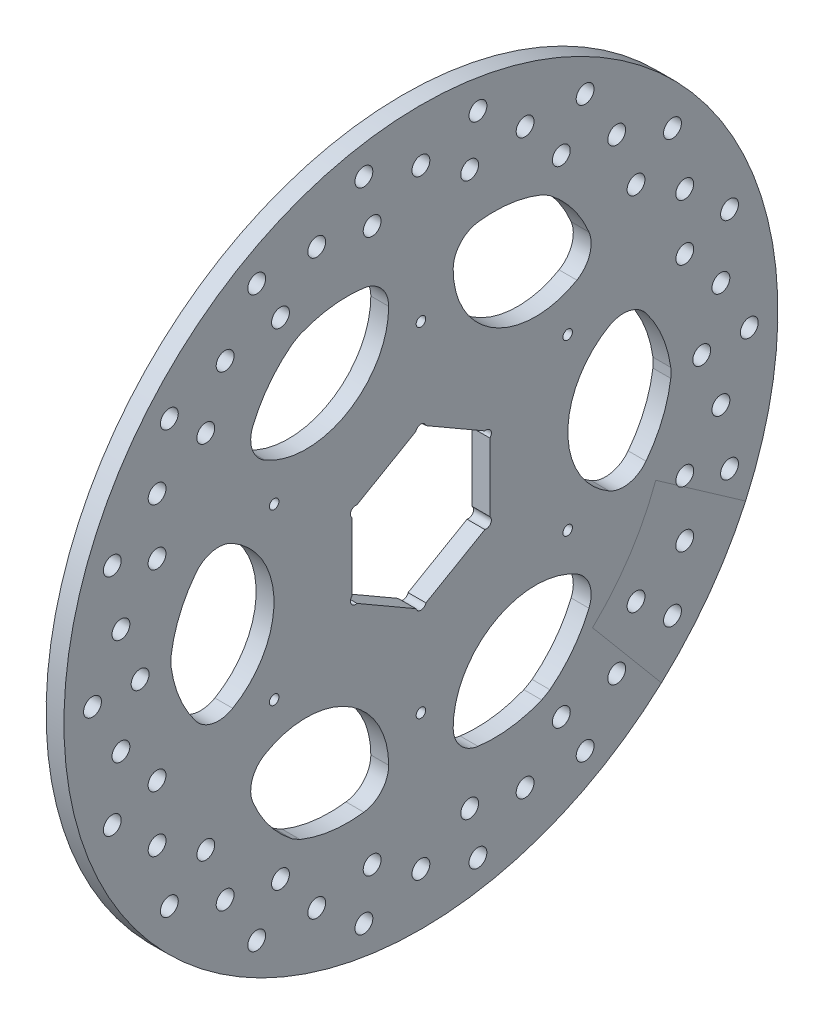
SolidWorks part; units mm, degrees
material "Gray Cast Iron (w/YS)"
ref_plane "X-Y Datum" through (0, 0, 0) normal (0, 0, 1) x (1, 0, 0)
ref_plane "X-Z Datum" through (0, 0, 0) normal (0, 1, 0) x (1, 0, 0)
ref_plane "Y-Z Datum" through (0, 0, 0) normal (1, 0, 0) x (0, 0, -1)
sketch "Sketch1" plane through (0, 0, 0) normal (1, 0, 0) x (0, 0, -1)
  circle A0 centre (0, 0) radius 95.25
  circle A1 centre (0, 0) radius 66.675
  dimension "D1" = 190.5
  dimension "D2" = 133.35
extrude "Main Rotor" add sketch "Sketch1" along normal blind 4.7625
sketch "Sketch2" plane through (4.7625, 0, 0) normal (1, 0, 0) x (0, 0, -1)
  line L0 (0, 0) -> (-50000, 0) construction
  line L1 (0, 0) -> (-93.8029, 16.54) construction
  line L4 (-82.3453, 29.9712) -> (-70.4112, 25.6276) construction
  circle A2 centre (0, 0) radius 95.25 construction
  circle A72 centre (-80.0452, 14.1141) radius 2.3813
  circle A73 centre (0, 0) radius 66.675 construction
  circle A74 centre (-82.3453, 29.9712) radius 2.3812
  circle A75 centre (-70.4112, 25.6276) radius 2.3813
  circle A76 centre (0, 0) radius 95.25 construction
  circle A77 centre (-70.3905, 40.64) radius 2.3812
  circle A78 centre (-67.1285, 56.3275) radius 2.3813
  circle A79 centre (0, 0) radius 66.675 construction
  circle A80 centre (-57.3997, 48.1641) radius 2.3813
  circle A81 centre (-52.2458, 62.2641) radius 2.3813
  circle A82 centre (-87.63, 0) radius 2.3813
  circle A83 centre (-43.815, 75.8898) radius 2.3812
  circle A84 centre (-37.465, 64.8913) radius 2.3813
  circle A85 centre (-74.93, 0) radius 2.3813
  circle A86 centre (-27.7994, 76.3782) radius 2.3812
  circle A87 centre (-15.2168, 86.2987) radius 2.3813
  circle A88 centre (-13.0115, 73.7916) radius 2.3813
  circle A89 centre (0, 81.28) radius 2.3813
  circle A90 centre (15.2168, 86.2987) radius 2.3813
  circle A91 centre (13.0115, 73.7916) radius 2.3813
  circle A92 centre (27.7994, 76.3782) radius 2.3813
  circle A93 centre (43.815, 75.8898) radius 2.3813
  circle A94 centre (37.465, 64.8913) radius 2.3813
  circle A95 centre (52.2458, 62.2641) radius 2.3813
  circle A96 centre (67.1285, 56.3275) radius 2.3813
  circle A97 centre (57.3997, 48.1641) radius 2.3813
  circle A98 centre (70.3905, 40.64) radius 2.3812
  circle A99 centre (82.3453, 29.9712) radius 2.3813
  circle A100 centre (70.4112, 25.6276) radius 2.3813
  circle A101 centre (80.0452, 14.1141) radius 2.3813
  circle A102 centre (87.63, 0) radius 2.3813
  circle A103 centre (74.93, 0) radius 2.3813
  circle A104 centre (80.0452, -14.1141) radius 2.3813
  circle A105 centre (82.3453, -29.9712) radius 2.3812
  circle A106 centre (70.4112, -25.6276) radius 2.3812
  circle A107 centre (70.3905, -40.64) radius 2.3813
  circle A108 centre (67.1285, -56.3275) radius 2.3812
  circle A109 centre (57.3997, -48.1641) radius 2.3813
  circle A110 centre (52.2458, -62.2641) radius 2.3812
  circle A111 centre (43.815, -75.8898) radius 2.3813
  circle A112 centre (37.465, -64.8913) radius 2.3813
  circle A113 centre (27.7994, -76.3782) radius 2.3813
  circle A114 centre (15.2168, -86.2987) radius 2.3813
  circle A115 centre (13.0115, -73.7916) radius 2.3812
  circle A116 centre (0, -81.28) radius 2.3812
  circle A117 centre (-15.2168, -86.2987) radius 2.3813
  circle A118 centre (-13.0115, -73.7916) radius 2.3813
  circle A119 centre (-27.7994, -76.3782) radius 2.3812
  circle A120 centre (-43.815, -75.8898) radius 2.3813
  circle A121 centre (-37.465, -64.8913) radius 2.3813
  circle A122 centre (-52.2458, -62.2641) radius 2.3813
  circle A123 centre (-67.1285, -56.3275) radius 2.3813
  circle A124 centre (-57.3997, -48.1641) radius 2.3813
  circle A125 centre (-70.3905, -40.64) radius 2.3813
  circle A126 centre (-82.3453, -29.9712) radius 2.3813
  circle A127 centre (-70.4112, -25.6276) radius 2.3813
  circle A128 centre (-80.0452, -14.1141) radius 2.3813
  point P109 (0, 0)
  dimension "D1" = 4.7625
  dimension "D2" = 12.7
  dimension "D3" = 10
  dimension "D5" = 81.28
  dimension "D4" = 87.63
  dimension "D6" = 18
extrude "Cut Slots" cut sketch "Sketch2" against normal through all
sketch "Sketch3" plane through (4.7625, 0, 0) normal (1, 0, 0) x (0, 0, -1)
  line L0 (0.3454, 5.0869) -> (-47951.5604, 14168.94) construction
  line L1 (0, 21.2491) -> (-18.4023, 10.6246)
  line L2 (-18.4023, 10.6246) -> (-18.4023, -10.6246)
  line L3 (-18.4023, -10.6246) -> (0, -21.2491)
  line L4 (0, -21.2491) -> (18.4023, -10.6246)
  line L5 (18.4023, -10.6246) -> (18.4023, 10.6246)
  line L6 (18.4023, 10.6246) -> (0, 21.2491)
  line L7 (0, 0) -> (43301.2702, 25000) construction
  line L8 (0, 0) -> (0, 50000) construction
  line L12 (9.525, -59.2994) -> (-9.525, -59.2994) construction
  line L17 (-30.6007, -53.002) -> (24969.3838, 43248.2414) construction
  line L18 (-60.783, 0) -> (49939.217, 0) construction
  line L19 (0, 0) -> (-25000, 43301.2702) construction
  line L20 (-14.2015, 9.3837) -> (0, 17.583) construction
  arc A0 (8.6043, -53.0208) -> (15.2264, -60.5686) centre (16.2243, -53.0143) ccw
  circle A1 centre (0, 0) radius 66.675 construction
  arc A7 (-15.2264, -60.5686) -> (-32.2316, -58.3668) centre (-19.5921, -27.5182) cw
  arc A10 (15.2264, -60.5686) -> (32.2316, -58.3668) centre (19.5921, -27.5182) ccw
  arc A19 (-19.6024, -33.9524) -> (-8.6043, -53.0208) centre (-30.6006, -53.0019) cw
  arc A25 (41.6152, -33.9619) -> (44.8408, -43.4707) centre (37.7996, -40.5577) cw
  arc A26 (34.4313, -57.0968) -> (66.6629, -1.27) centre (0, 0) ccw
  arc A27 (50.2195, -19.0589) -> (60.0672, -17.0979) centre (54.0238, -12.4565) ccw
  arc A28 (19.6024, -33.9524) -> (8.6043, -53.0208) centre (30.6006, -53.0019) ccw
  arc A29 (60.0672, 17.0979) -> (50.2195, 19.0589) centre (54.0238, 12.4565) ccw
  arc A30 (-44.8408, -43.4707) -> (-34.4313, -57.0968) centre (-14.0354, -30.7264) ccw
  arc A31 (-19.6024, -33.9524) -> (-41.6152, -33.9619) centre (-30.6006, -53.0019) ccw
  arc A32 (-39.2049, 0) -> (-50.2195, -19.0589) centre (-61.2013, 0) cw
  arc A33 (-60.0672, -17.0979) -> (-66.6629, -1.27) centre (-33.6275, 3.2082) cw
  arc A34 (-60.0672, 17.0979) -> (-66.6629, 1.27) centre (-33.6275, -3.2082) ccw
  arc A35 (44.8408, 43.4707) -> (41.6152, 33.9619) centre (37.7996, 40.5577) cw
  arc A36 (-32.2316, -58.3668) -> (32.2316, -58.3668) centre (0, 0) ccw
  arc A37 (15.2264, 60.5686) -> (8.6043, 53.0208) centre (16.2243, 53.0143) ccw
  arc A38 (-8.6043, 53.0208) -> (-15.2264, 60.5686) centre (-16.2243, 53.0143) ccw
  arc A39 (-44.8408, 43.4707) -> (-41.6152, 33.9619) centre (-37.7996, 40.5577) ccw
  arc A40 (-50.2195, 19.0589) -> (-60.0672, 17.0979) centre (-54.0238, 12.4565) ccw
  arc A41 (-50.2195, -19.0589) -> (-60.0672, -17.0979) centre (-54.0238, -12.4565) cw
  arc A42 (-8.6043, -53.0208) -> (-15.2264, -60.5686) centre (-16.2243, -53.0143) cw
  arc A43 (-41.6152, -33.9619) -> (-44.8408, -43.4707) centre (-37.7996, -40.5577) ccw
  arc A44 (-39.2049, 0) -> (-50.2195, 19.0589) centre (-61.2013, 0) ccw
  arc A45 (-19.6025, 33.9524) -> (-41.6152, 33.9619) centre (-30.6007, 53.0019) cw
  arc A46 (-44.8408, 43.4707) -> (-34.4313, 57.0968) centre (-14.0354, 30.7264) cw
  arc A47 (-15.2264, 60.5686) -> (-32.2316, 58.3668) centre (-19.5921, 27.5182) ccw
  arc A48 (-19.6025, 33.9524) -> (-8.6043, 53.0208) centre (-30.6007, 53.0019) ccw
  arc A49 (19.6024, 33.9524) -> (8.6043, 53.0208) centre (30.6006, 53.0019) cw
  arc A50 (15.2264, 60.5686) -> (32.2316, 58.3668) centre (19.5921, 27.5182) cw
  arc A51 (44.8408, 43.4707) -> (34.4313, 57.0968) centre (14.0354, 30.7264) ccw
  arc A52 (19.6024, 33.9524) -> (41.6152, 33.9619) centre (30.6006, 53.0019) ccw
  arc A53 (39.2049, 0) -> (50.2195, 19.0589) centre (61.2013, 0) cw
  arc A54 (60.0672, 17.0979) -> (66.6629, 1.27) centre (33.6275, -3.2082) cw
  arc A55 (60.0672, -17.0979) -> (66.6629, -1.27) centre (33.6275, 3.2082) ccw
  arc A56 (39.2049, 0) -> (50.2195, -19.0589) centre (61.2013, 0) ccw
  arc A57 (19.6024, -33.9524) -> (41.6152, -33.9619) centre (30.6007, -53.0019) cw
  arc A58 (44.8408, -43.4707) -> (34.4313, -57.0968) centre (14.0354, -30.7264) cw
  circle A59 centre (0, 20.1061) radius 1.3891
  arc A60 (-66.6629, -1.27) -> (-34.4313, -57.0968) centre (0, 0) ccw
  arc A62 (-34.4313, 57.0968) -> (-66.6629, 1.27) centre (0, 0) ccw
  arc A64 (32.2316, 58.3668) -> (-32.2316, 58.3668) centre (0, 0) ccw
  arc A66 (66.6629, 1.27) -> (34.4313, 57.0968) centre (0, 0) ccw
  circle A71 centre (0, 0) radius 7.4362 construction
  circle A72 centre (0, 17.583) radius 3.175 construction
  circle A73 centre (17.4124, 10.0531) radius 1.3891
  circle A74 centre (17.4124, -10.0531) radius 1.3891
  circle A75 centre (0, -20.1061) radius 1.3891
  circle A76 centre (-17.4124, -10.0531) radius 1.3891
  circle A77 centre (-17.4124, 10.0531) radius 1.3891
  point P34 (0, -59.2994)
  point P35 (-9.2012, 15.9369)
  point P116 (0, 0)
  point P124 (0, 0)
  dimension "D2" = 42.799
  dimension "D4" = 7.62
  dimension "D7" = 1.27
  dimension "D8" = 33.3375
  dimension "D9" = 21.9964
  dimension "D10" = 2.7781
  dimension "D11" = 3.175
  dimension "D12" = 6.35
  dimension "D13" = 6
  dimension "D1" = 36.8046
  dimension "D3" = 6
  dimension "D5" = 1.143
  dimension "D6" = 19.05
extrude "Boss-Extrude2" add sketch "Sketch3" against normal up to surface (4.7625 mm away) contours A54 A66 A51 A35 A52 A49 A37 A50 A64 A47 A38 A48 A45 A39 A46 A62 A34 A40 A44 A32 A41 A33 A60 A30 A43 A31 A19 A42 A7 A36 A10 A0 A28 A57 A25 A58 A26 A55 A27 A56 A53 A29 L1 A59 L6 L5 L4 region at (4.7625, -59.2833, -9.0788) up to face at (0, 0, 85.2488)
fillet "Fillet1" [suppressed] radius 3.175
sketch "Sketch4" plane through (0, 0, 0) normal (-1, 0, 0) x (0, 0, 1)
  circle A0 centre (0, 45.212) radius 1.27
  circle A1 centre (39.1547, 22.606) radius 1.27
  circle A2 centre (39.1547, -22.606) radius 1.27
  circle A3 centre (0, -45.212) radius 1.27
  circle A4 centre (-39.1547, -22.606) radius 1.27
  circle A5 centre (-39.1547, 22.606) radius 1.27
  point P16 (0, 0)
  dimension "D1" = 45.212
  dimension "D2" = 2.54
  dimension "D3" = 6
extrude "Cut-Extrude2" cut sketch "Sketch4" against normal through all
sketch "Sketch5" plane through (4.7625, 0, 0) normal (1, 0, 0) x (0, 0, -1)
  line L0 (0, 0) -> (-50000, 0) construction
  line L1 (0, 0) -> (-46984.631, 17101.0072) construction
  line L2 (62.654, -22.8042) -> (86.6311, -39.5931)
  line L3 (45.7933, -48.4616) -> (64.1833, -70.378)
  circle A0 centre (0, 0) radius 95.25 construction
  circle A1 centre (0, 0) radius 66.675 construction
  arc A2 (64.1833, -70.378) -> (86.6311, -39.5931) centre (0, 0) ccw
  arc A3 (45.7933, -48.4616) -> (62.654, -22.8042) centre (0, 0) ccw
  dimension "D1" = 20
  dimension "D2" = 15
  dimension "D3" = 15
  dimension "D4" = 38.1
split line "Split Line1"
ref_axis "Axis1" through (5.0006, 0, 0) along (-1, 0, 0)
